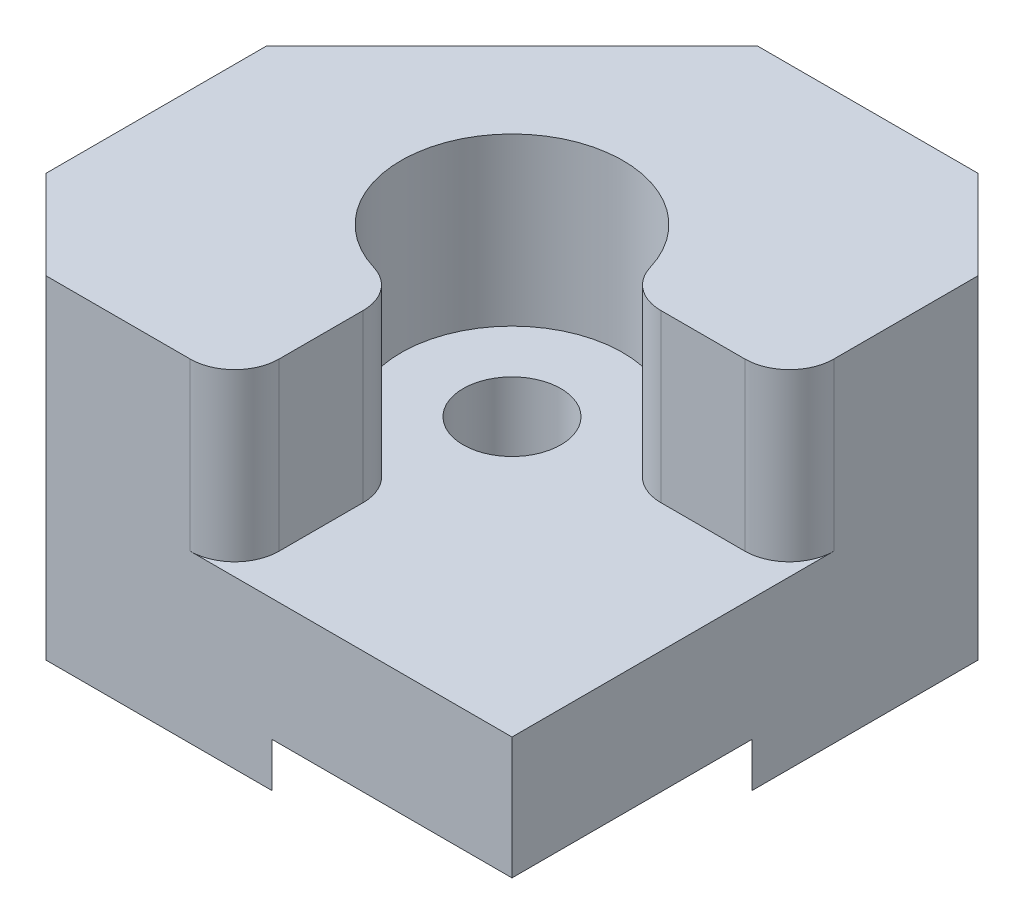
SolidWorks part; units mm, degrees
ref_plane "Front Plane" through (0, 0, 0) normal (0, 0, 1) x (1, 0, 0)
ref_plane "Top Plane" through (0, 0, 0) normal (0, 1, 0) x (1, 0, 0)
ref_plane "Right Plane" through (0, 0, 0) normal (1, 0, 0) x (0, 0, -1)
sketch "ｽｹｯﾁ1" plane through (0, 0, 0) normal (0, 1, 0) x (1, 0, 0)
  line L1 (-12.5, 12.5) -> (12.5, 12.5)
  line L2 (-12.5, 12.5) -> (-12.5, -12.5)
  line L3 (-12.5, -12.5) -> (12.5, -12.5)
  line L4 (12.5, 12.5) -> (12.5, -12.5)
  line L5 (0, -12.5) -> (0, 12.5) construction
  line L6 (-12.5, 0) -> (12.5, 0) construction
  point P0 (0, 0)
  dimension "D1" = 25
extrude "ﾎﾞｽ - 押し出し1" add sketch "ｽｹｯﾁ1" along normal mid plane 15
sketch "ｽｹｯﾁ2" plane through (0, 7.5, 0) normal (0, 1, 0) x (1, 0, 0)
  line L2 (12.5, -12.5) -> (12.5, 12.5) construction
  line L3 (12.5, 0) -> (5, 0)
  line L4 (0, -5) -> (0, -12.5)
  line L5 (-12.5, -12.5) -> (12.5, -12.5) construction
  line L8 (0, -12.5) -> (12.5, -12.5)
  line L9 (12.5, -12.5) -> (12.5, 0)
  arc A1 (5, 0) -> (0, -5) centre (0, 0) ccw
  dimension "D1" = 5
extrude "ｶｯﾄ - 押し出し3" cut sketch "ｽｹｯﾁ2" against normal up to surface (7.5 mm away) up to plane "Top Plane"
sketch "ｽｹｯﾁ4" plane through (0, 0, 0) normal (0, 1, 0) x (1, 0, 0)
  circle A0 centre (0, 0) radius 2.2
  dimension "D1" = 4.4
extrude "ｶｯﾄ - 押し出し4" cut sketch "ｽｹｯﾁ4" against normal through all
sketch "ｽｹｯﾁ5" plane through (0, -7.5, 0) normal (0, -1, 0) x (1, 0, 0)
  line L0 (-12.5, -1.6813) -> (1.6813, 12.5)
  line L1 (-12.5, -12.5) -> (-12.5, 12.5) construction
  line L2 (-12.5, 12.5) -> (12.5, 12.5) construction
  line L3 (1.6813, 12.5) -> (12.5, 12.5)
  line L4 (12.5, 12.5) -> (12.5, 1.6813)
  line L5 (12.5, 12.5) -> (12.5, -12.5) construction
  line L6 (12.5, 1.6813) -> (-1.6813, -12.5)
  line L7 (12.5, -12.5) -> (-12.5, -12.5) construction
  line L8 (-1.6813, -12.5) -> (-12.5, -12.5)
  line L9 (-12.5, -12.5) -> (-12.5, -1.6813)
  line L10 (-5.4094, 5.4094) -> (5.4094, -5.4094) construction
  point P20 (0, 0)
  dimension "D1" = 15.3
extrude "ｶｯﾄ - 押し出し5" cut sketch "ｽｹｯﾁ5" against normal blind 2
sketch "ｽｹｯﾁ6" [suppressed] plane through (0, 7.5, 0) normal (0, 1, 0) x (1, 0, 0)
  line L0 (0, 0) -> (-3.5355, 3.5355) construction
  line L1 (12.5, -12.5) -> (0, -12.5)
  line L2 (12.5, -12.5) -> (12.5, 0)
  line L3 (12.5, 0) -> (0, 0)
  line L4 (0, -12.5) -> (0, 0)
  circle A0 centre (-3.5355, 3.5355) radius 3.7
  circle A1 centre (0, 0) radius 0.5
  dimension "D2" = 7.4
  dimension "D4" = 1
  dimension "D1" = 45
  dimension "D3" = 5
extrude "ｶｯﾄ - 押し出し6" [suppressed] cut sketch "ｽｹｯﾁ6" against normal up to surface (7.5 mm away)
sketch "ｽｹｯﾁ7" [suppressed] plane through (0, 0, 0) normal (0, 1, 0) x (1, 0, 0)
  circle A0 centre (-3.5355, 3.5355) radius 2.25
  dimension "D1" = 4.5
extrude "ｶｯﾄ - 押し出し7" [suppressed] cut sketch "ｽｹｯﾁ7" against normal through all
chamfer "面取り1" distance 4 angle 45 3 edges at (12.5, 0, -12.5) (-12.5, 1, -12.5) (-12.5, 0, 12.5)
chamfer "面取り2" distance 5 angle 45 1 edges at (-10.5, 7.5, -10.5)
fillet "ﾌｨﾚｯﾄ2" [suppressed] radius 2
fillet "ﾌｨﾚｯﾄ3" radius 2 4 edges at (12.5, 3.75, 0) (0, 3.75, 12.5) (0, 3.75, 5) (5, 3.75, 0)
sketch "ｽｹｯﾁ8" [suppressed] plane through (0, 0, 0) normal (0, 1, 0) x (1, 0, 0)
  line L4 (0, -1.5) -> (0, -10.5)
  line L5 (-2, -12.5) -> (12.5, -12.5)
  line L6 (12.5, -12.5) -> (12.5, 2)
  line L7 (10.5, 0) -> (1.5, 0)
  line L8 (0, -1.5) -> (0, -10.5)
  line L9 (-2, -12.5) -> (12.5, -12.5)
  line L10 (12.5, -12.5) -> (12.5, 2)
  line L11 (10.5, 0) -> (1.5, 0)
  arc A5 (0.3, 0.4) -> (-0.4, -0.3) centre (0, 0) ccw
  arc A6 (0, -1.5) -> (-0.4, -0.3) centre (-2, -1.5) ccw
  arc A7 (-2, -12.5) -> (0, -10.5) centre (-2, -10.5) ccw
  arc A8 (10.5, 0) -> (12.5, 2) centre (10.5, 2) ccw
  arc A9 (0.3, 0.4) -> (1.5, 0) centre (1.5, 2) ccw
  arc A10 (0.3, 0.4) -> (-0.4, -0.3) centre (0, 0) ccw
  arc A11 (0, -1.5) -> (-0.4, -0.3) centre (-2, -1.5) ccw
  arc A12 (-2, -12.5) -> (0, -10.5) centre (-2, -10.5) ccw
  arc A13 (10.5, 0) -> (12.5, 2) centre (10.5, 2) ccw
  arc A14 (0.3, 0.4) -> (1.5, 0) centre (1.5, 2) ccw
  dimension "D1" = 0
extrude "ﾎﾞｽ - 押し出し2" [suppressed] add sketch "ｽｹｯﾁ8" along normal up to surface (5.5 mm away) from offset 2
